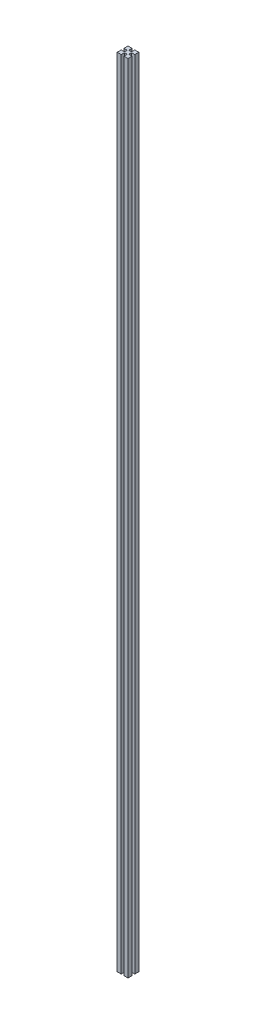
SolidWorks part; units mm, degrees
ref_plane "Front Plane" through (0, 0, 0) normal (0, 0, 1) x (1, 0, 0)
ref_plane "Top Plane" through (0, 0, 0) normal (0, 1, 0) x (1, 0, 0)
ref_plane "Right Plane" through (0, 0, 0) normal (1, 0, 0) x (0, 0, -1)
sketch "Sketch1" plane through (0, 0, 0) normal (0, 1, 0) x (1, 0, 0)
  line L1 (-10, -10) -> (10, -10)
  line L2 (-10, -10) -> (-10, 10)
  line L3 (-10, 10) -> (10, 10)
  line L4 (10, -10) -> (10, 10)
  line L5 (-10, -10) -> (10, 10) construction
  line L6 (-10, 10) -> (10, -10) construction
  point P0 (0, 0)
  dimension "D1" = 20
  dimension "D2" = 20
extrude "Boss-Extrude1" add sketch "Sketch1" along normal blind 736.6 and the other way blind 736.6
sketch "Sketch2" plane through (0, 0, 0) normal (0, 1, 0) x (1, 0, 0)
  line L0 (-2.5, 4) -> (2.5, 4)
  line L1 (-2.5, 4) -> (-2.5, 16)
  line L2 (-2.5, 16) -> (2.5, 16)
  line L3 (2.5, 4) -> (2.5, 16)
  line L4 (-2.5, 4) -> (2.5, 16) construction
  line L5 (-2.5, 16) -> (2.5, 4) construction
  line L6 (4, 2.5) -> (16, 2.5)
  line L7 (4, 2.5) -> (4, -2.5)
  line L8 (4, -2.5) -> (16, -2.5)
  line L9 (16, 2.5) -> (16, -2.5)
  line L10 (4, 2.5) -> (16, -2.5) construction
  line L11 (4, -2.5) -> (16, 2.5) construction
  line L12 (-10, 10) -> (10, -10) construction
  line L13 (-16, 2.5) -> (-4, -2.5) construction
  line L14 (-4, 2.5) -> (-16, -2.5) construction
  line L15 (-4, -2.5) -> (-16, -2.5)
  line L16 (-16, 2.5) -> (-16, -2.5)
  line L17 (-4, 2.5) -> (-16, 2.5)
  line L18 (-4, 2.5) -> (-4, -2.5)
  line L19 (2.5, -4) -> (2.5, -16)
  line L20 (2.5, -4) -> (-2.5, -16) construction
  line L21 (-2.5, -4) -> (2.5, -16) construction
  line L22 (-2.5, -16) -> (2.5, -16)
  line L23 (-2.5, -4) -> (2.5, -4)
  line L24 (-2.5, -4) -> (-2.5, -16)
  line L25 (10, 10) -> (-10, 10) construction
  line L26 (10, -10) -> (10, 10) construction
  point P0 (0, 10)
  point P5 (10, 0)
  point P16 (-10, 0)
  point P21 (0, -10)
  dimension "D1" = 5
  dimension "D2" = 12
  dimension "D3" = 5
  dimension "D4" = 12
extrude "Cut-Extrude1" cut sketch "Sketch2" against normal through all both and the other way through all
